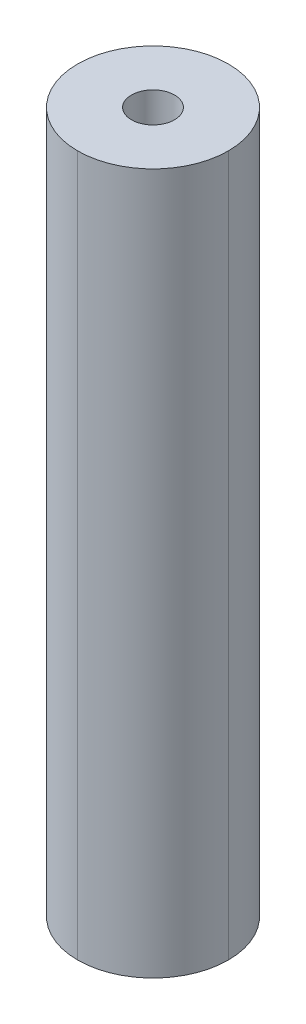
SolidWorks part; units mm, degrees
ref_plane "Front Plane" through (0, 0, 0) normal (0, 0, 1) x (1, 0, 0)
ref_plane "Top Plane" through (0, 0, 0) normal (0, 1, 0) x (1, 0, 0)
ref_plane "Right Plane" through (0, 0, 0) normal (1, 0, 0) x (0, 0, -1)
sketch "Sketch1" plane through (0, 0, 0) normal (0, 1, 0) x (1, 0, 0)
  line L5 (-7, 7) -> (7, 7)
  line L6 (-7, 7) -> (-7, -7)
  line L7 (-7, -7) -> (7, -7)
  line L8 (7, 7) -> (7, -7)
  line L9 (-7, 7) -> (7, -7) construction
  line L10 (-7, -7) -> (7, 7) construction
  point P0 (0, 0)
  dimension "D1" = 14
  dimension "D2" = 14
extrude "Boss-Extrude2" add sketch "Sketch1" along normal blind 65.1
sketch "Sketch2" plane through (0, 65.1, 0) normal (0, 1, 0) x (1, 0, 0)
  circle A0 centre (0, 0) radius 2
  dimension "D1" = 4
extrude "Cut-Extrude1" cut sketch "Sketch2" against normal through all
fillet "Fillet1" radius 7 4 edges at (-7, 32.55, 7) (-7, 32.55, -7) (7, 32.55, -7) (7, 32.55, 7)
